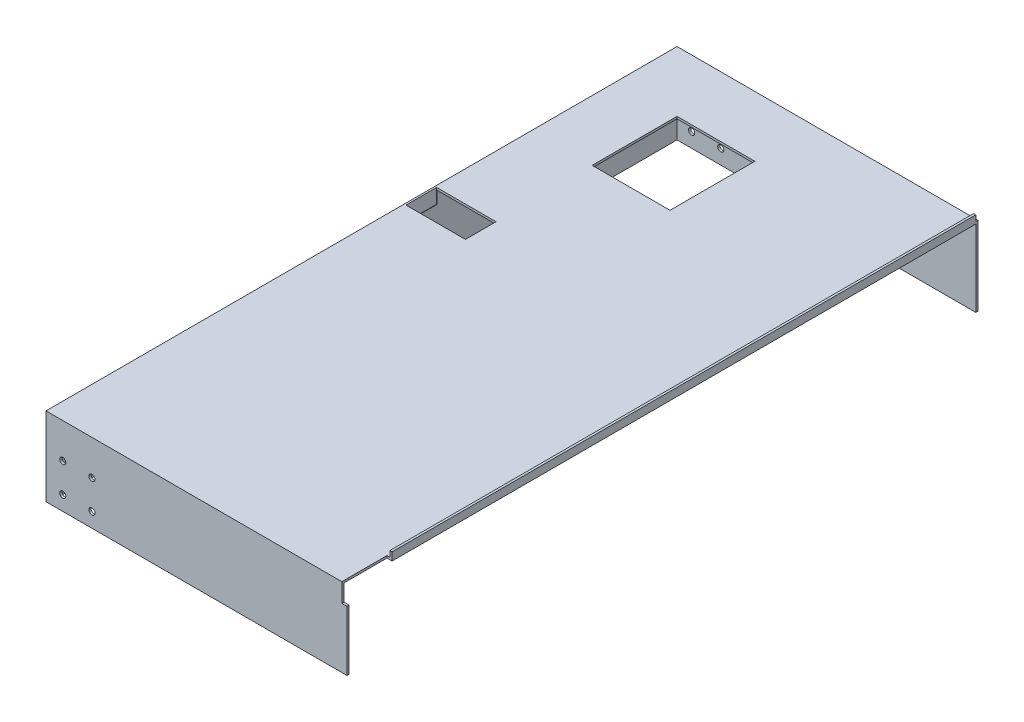
SolidWorks part; units mm, degrees
ref_plane "Front Plane" through (0, 0, 0) normal (0, 0, 1) x (1, 0, 0)
ref_plane "Top Plane" through (0, 0, 0) normal (0, 1, 0) x (1, 0, 0)
ref_plane "Right Plane" through (0, 0, 0) normal (1, 0, 0) x (0, 0, -1)
sketch "Sketch4" plane through (0, 0, 0) normal (0, 1, 0) x (1, 0, 0)
  line L0 (124.0135, 430) -> (329.0135, 430)
  line L1 (329.0135, 430) -> (329.0135, 0)
  line L2 (329.0135, 0) -> (124.0135, 0)
  line L3 (124.0135, 0) -> (124.0135, 200)
  line L7 (124.0135, 365) -> (124.0135, 430)
  line L8 (124.0135, 200) -> (124.0135, 365)
  line L9 (329.0135, 80.0946) -> (329.0135, 106.0946) construction
  point P3 (329.0135, 0)
  point P10 (0, 0)
  point P11 (0, 0)
  point P12 (0, 0)
  point P13 (0, 0)
  dimension "D2" = 65
  dimension "D4" = 200
  dimension "D5" = 205
  dimension "D6" = 205
extrude "Boss-Extrude4" add sketch "Sketch4" along normal blind 1.5 separate body
sketch "Sketch5" plane through (0, 0, 0) normal (0, 0, 1) x (1, 0, 0)
  line L1 (124.0135, 1.5) -> (329.0135, 1.5)
  line L2 (124.0135, 1.5) -> (124.0135, -52.5)
  line L3 (124.0135, -52.5) -> (329.0135, -52.5)
  line L4 (329.0135, 1.5) -> (329.0135, -52.5)
  dimension "D1" = 54
sketch "Sketch7" plane through (0, 0, -430) normal (0, 0, -1) x (-1, 0, 0)
  line L1 (-124.0135, 1.5) -> (-329.0135, 1.5)
  line L2 (-124.0135, 1.5) -> (-124.0135, -52.5)
  line L3 (-124.0135, -52.5) -> (-329.0135, -52.5)
  line L4 (-329.0135, 1.5) -> (-329.0135, -52.5)
  dimension "D1" = 54
  dimension "D2" = 205
sketch "Sketch8" plane through (0, 1.5, 0) normal (0, 1, 0) x (1, 0, 0)
  line L0 (124.0135, 430) -> (329.0135, 430) construction
  line L1 (329.0135, 0) -> (327.5135, 0)
  line L2 (329.0135, 0) -> (329.0135, 430)
  line L3 (329.0135, 430) -> (327.5135, 430)
  line L4 (327.5135, 0) -> (327.5135, 430)
  dimension "D1" = 1.5
extrude "Boss-Extrude5" add sketch "Sketch5" along normal blind 1.5
extrude "Boss-Extrude14" add sketch "Sketch8" along normal blind 4
extrude "Boss-Extrude18" add sketch "Sketch7" along normal blind 1.5
sketch "Sketch9" plane through (124.0135, 0, 0) normal (-1, 0, 0) x (0, 0, 1)
  line L1 (-431.5, 1.5) -> (1.5, 1.5)
  line L2 (-431.5, 1.5) -> (-431.5, -52.5)
  line L3 (-431.5, -52.5) -> (1.5, -52.5)
  line L4 (1.5, 1.5) -> (1.5, -52.5)
extrude "Boss-Extrude19" add sketch "Sketch9" along normal blind 1.5
sketch "Sketch10" plane through (0, 0, -431.5) normal (0, 0, -1) x (-1, 0, 0)
  circle A0 centre (-154.0135, -42.5) radius 2.1
  point P3 (-209.4784, -42.5)
  point P4 (-154.7269, -46.4115)
  point P5 (-154.0135, -42.5)
sketch "Sketch11" plane through (0, 0, -431.5) normal (0, 0, -1) x (-1, 0, 0)
  circle A0 centre (-134.0237, -42.5218) radius 2.1
  point P3 (0, 0)
  point P4 (-134.0802, -42.4277)
  point P5 (-134.0237, -42.5218)
sketch "Sketch12" plane through (0, 0, -431.5) normal (0, 0, -1) x (-1, 0, 0)
  circle A0 centre (-134.0173, -22.4773) radius 2.1
  point P3 (0, 0)
  point P4 (-133.294, -22.8919)
  point P5 (-134.0173, -22.4773)
sketch "Sketch13" plane through (0, 0, -431.5) normal (0, 0, -1) x (-1, 0, 0)
  circle A0 centre (-154.0032, -22.5144) radius 2.1
  point P3 (0, 0)
  point P4 (-154.0477, -22.5835)
  point P5 (-154.0032, -22.5144)
sketch "Sketch14" plane through (0, 0, 1.5) normal (0, 0, 1) x (1, 0, 0)
  circle A0 centre (134.0173, -22.4773) radius 2.1
sketch "Sketch15" plane through (0, 0, 1.5) normal (0, 0, 1) x (1, 0, 0)
  circle A0 centre (154.0032, -22.5144) radius 2.1
sketch "Sketch16" plane through (0, 0, 1.5) normal (0, 0, 1) x (1, 0, 0)
  circle A0 centre (134.0237, -42.5218) radius 2.1
sketch "Sketch17" plane through (0, 0, 1.5) normal (0, 0, 1) x (1, 0, 0)
  circle A0 centre (154.0135, -42.5) radius 2.1
  point P3 (0, 0)
  point P4 (153.8504, -42.4642)
  point P5 (154.0135, -42.5)
extrude "Cut-Extrude1" cut sketch "Sketch10" against normal blind 10
extrude "Cut-Extrude2" cut sketch "Sketch17" against normal blind 10
extrude "Cut-Extrude3" cut sketch "Sketch16" against normal blind 10
extrude "Cut-Extrude4" cut sketch "Sketch11" against normal blind 10
extrude "Cut-Extrude5" cut sketch "Sketch12" against normal blind 10
extrude "Cut-Extrude6" cut sketch "Sketch13" against normal blind 10
extrude "Cut-Extrude7" cut sketch "Sketch14" against normal blind 10
extrude "Cut-Extrude8" cut sketch "Sketch15" against normal blind 10
sketch "Sketch18" plane through (0, 1.5, 0) normal (0, 1, 0) x (1, 0, 0)
  line L1 (123.7353, 265.2813) -> (164.512, 265.2813)
  line L2 (123.7353, 265.2813) -> (123.7353, 244.2776)
  line L3 (123.7353, 244.2776) -> (164.512, 244.2776)
  line L4 (164.512, 265.2813) -> (164.512, 244.2776)
extrude "Cut-Extrude9" cut sketch "Sketch18" against normal blind 10
sketch "Sketch21" plane through (0, 1.5, 0) normal (0, 1, 0) x (1, 0, 0)
  line L1 (164.0135, 390) -> (217.4083, 390)
  line L2 (164.0135, 390) -> (164.0135, 331.7654)
  line L3 (164.0135, 331.7654) -> (217.4083, 331.7654)
  line L4 (217.4083, 390) -> (217.4083, 331.7654)
  point P5 (0, 0)
  point P6 (164.0135, 390.75)
extrude "Cut-Extrude12" cut sketch "Sketch21" against normal blind 10
sketch "Sketch23" plane through (0, 0, 1.5) normal (0, 0, 1) x (1, 0, 0)
  line L1 (325.5003, 6.2283) -> (329.0135, 6.2283)
  line L2 (325.5003, 6.2283) -> (325.5003, -11.4156)
  line L3 (325.5003, -11.4156) -> (329.0135, -11.4156)
  line L4 (329.0135, 6.2283) -> (329.0135, -11.4156)
  point P6 (0, 0)
extrude "Cut-Extrude14" cut sketch "Sketch23" against normal blind 31
